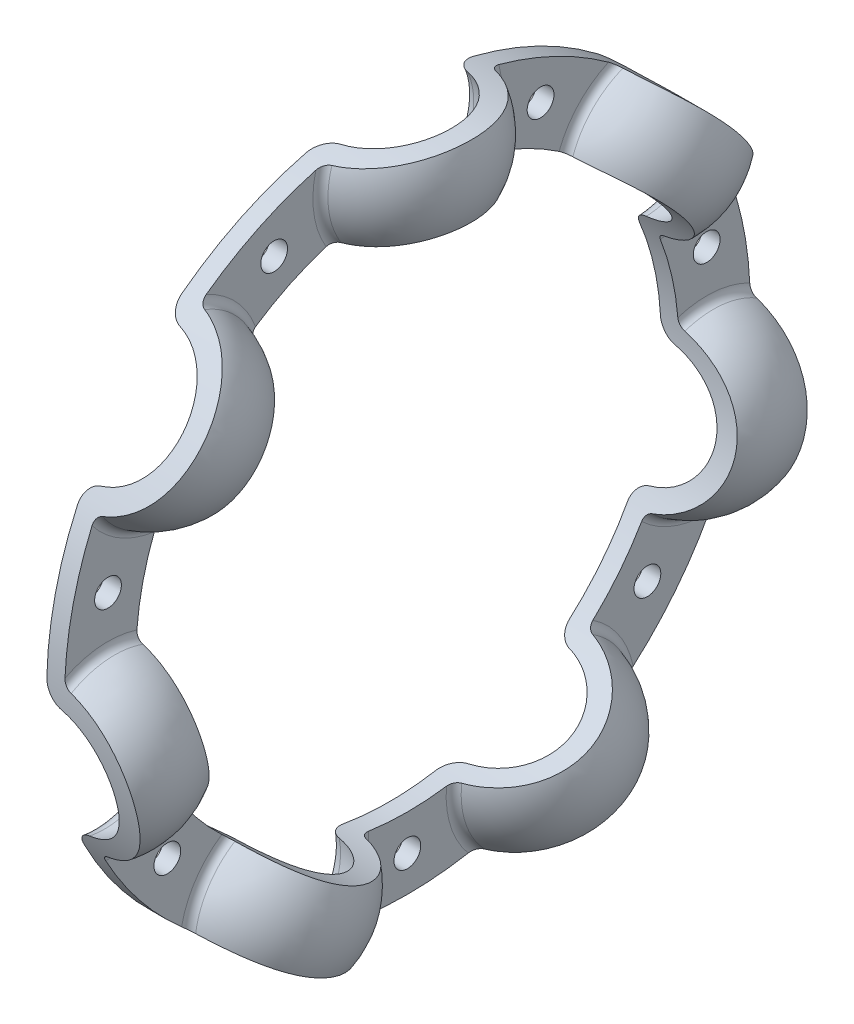
SolidWorks part; units mm, degrees
ref_plane "Front Plane" through (0, 0, 0) normal (0, 0, 1) x (1, 0, 0)
ref_plane "Top Plane" through (0, 0, 0) normal (0, 1, 0) x (1, 0, 0)
ref_plane "Right Plane" through (0, 0, 0) normal (1, 0, 0) x (0, 0, -1)
sketch "Sketch1" plane through (0, 0, 0) normal (1, 0, 0) x (0, 0, -1)
  circle A0 centre (0, 0) radius 25
  dimension "D1" = 50
extrude "Boss-Extrude1" add sketch "Sketch1" along normal blind 1
sketch "Sketch2" plane through (0, 0, 0) normal (-1, 0, 0) x (0, 0, 1)
  line L0 (-5, 17.2) -> (5, 17.2)
  line L1 (0, 17.2) -> (0, 0) construction
  arc A0 (-5, 17.2) -> (5, 17.2) centre (0, 17.2) ccw
  dimension "D2" = 5
  dimension "D1" = 17.2
revolve "Revolve1" add sketch "Sketch2" angle 180 about L0
sketch "Sketch3" plane through (0, 0, 0) normal (-1, 0, 0) x (0, 0, 1)
  line L0 (-4, 17.2) -> (4, 17.2)
  line L1 (0, 17.2) -> (0, 0) construction
  arc A0 (-4, 17.2) -> (4, 17.2) centre (0, 17.2) cw
  dimension "D2" = 4
  dimension "D1" = 17.2
revolve "Cut-Revolve1" cut sketch "Sketch3" angle 180 about L0 reverse direction yes
fillet "Fillet1" radius 0.5 1 edges at (1, 17.2, -4.899)
fillet "Fillet2" radius 1 1 edges at (0, 17.2, -4)
pattern_circular "CirPattern1" count 7 over 360 about axis through (1, 0, 0) along (1, 0, 0) of "Revolve1", "Cut-Revolve1", "Fillet2", "Fillet1"
sketch "Sketch4" plane through (1, 0, 0) normal (1, 0, 0) x (0, 0, -1)
  circle A0 centre (0, 0) radius 19.2
  circle A1 centre (0, 0) radius 25
  circle A2 centre (0, 0) radius 17.2 construction
  circle A3 centre (0, 0) radius 25 construction
  dimension "D1" = 34.4
  dimension "D2" = 2
extrude "Cut-Extrude1" cut sketch "Sketch4" against normal through all both and the other way through all
sketch "Sketch5" plane through (1, 0, 0) normal (1, 0, 0) x (0, 0, -1)
  circle A0 centre (0, 0) radius 15.2
  arc A1 (-17.6634, 7.5262) -> (-19.1797, 0.883) centre (0, 0) ccw construction
  dimension "D1" = 4
extrude "Cut-Extrude2" cut sketch "Sketch5" against normal through all both and the other way through all
sketch "Sketch6" plane through (1, 0, 0) normal (1, 0, 0) x (0, 0, -1)
  line L0 (0, 0) -> (0, -17.2) construction
  circle A0 centre (0, -17.2) radius 0.75
  dimension "D2" = 1.5
  dimension "D1" = 17.2
extrude "Cut-Extrude3" cut sketch "Sketch6" against normal blind 1
pattern_circular "CirPattern2" count 7 over 360 about axis through (1, 0, 0) along (1, 0, 0) of "Cut-Extrude3"
